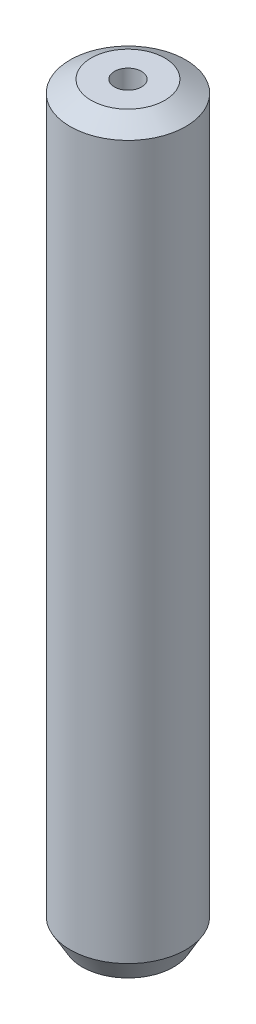
SolidWorks part; units mm, degrees
ref_plane "Front Plane" through (0, 0, 0) normal (0, 0, 1) x (1, 0, 0)
ref_plane "Top Plane" through (0, 0, 0) normal (0, 1, 0) x (1, 0, 0)
ref_plane "Right Plane" through (0, 0, 0) normal (1, 0, 0) x (0, 0, -1)
sketch "Sketch1" plane through (0, 0, 0) normal (0, 1, 0) x (1, 0, 0)
  circle A0 centre (0, 0) radius 7.5
  dimension "SHAFT_OD" = 15
extrude "Boss-Extrude1" add sketch "Sketch1" along normal blind 96.8
sketch "Sketch2" plane through (0, 0, 0) normal (0, 1, 0) x (1, 0, 0)
  circle A0 centre (0, 0) radius 1.7584
  dimension "BORE_D" = 3.5169
extrude "Cut-Extrude1" cut sketch "Sketch2" along normal through all
chamfer "Chamfer1" distance 1.5766 angle 60 2 edges at (0, 96.8, 7.5) (0, 0, 7.5) first distance on face at (0, 96.8, 7.5) first distance on face at (0, 0, 1.7584)
